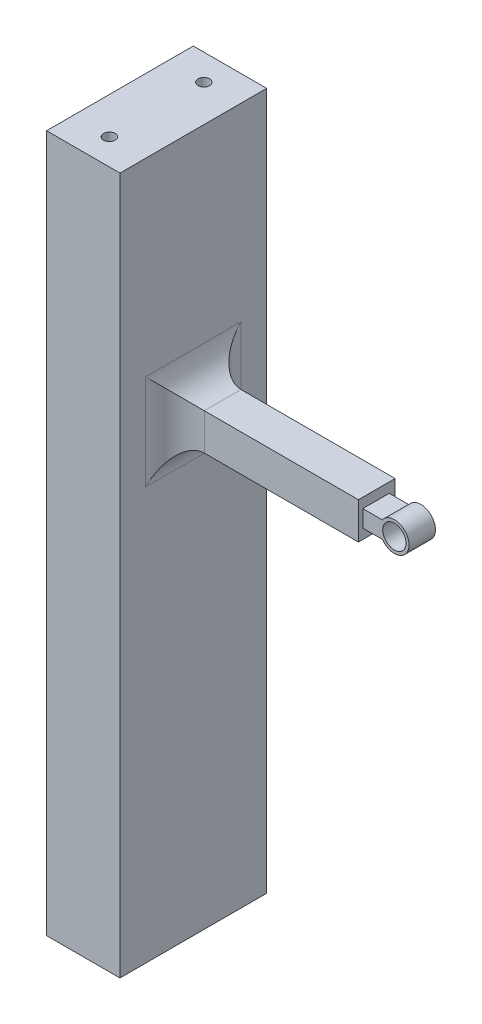
SolidWorks part; units mm, degrees
ref_plane "Front Plane" through (0, 0, 0) normal (0, 0, 1) x (1, 0, 0)
ref_plane "Top Plane" through (0, 0, 0) normal (0, 1, 0) x (1, 0, 0)
ref_plane "Right Plane" through (0, 0, 0) normal (1, 0, 0) x (0, 0, -1)
sketch "Sketch1" plane through (0, 0, 0) normal (0, 0, 1) x (1, 0, 0)
  line L0 (-112.8647, 1033.9699) -> (-112.8647, -66.0301)
  line L1 (-112.8647, 1033.9699) -> (-212.8647, 1033.9699)
  line L2 (-212.8647, 1033.9699) -> (-212.8647, -66.0301)
  line L3 (-212.8647, -66.0301) -> (-112.8647, -66.0301)
extrude "Boss-Extrude1" add sketch "Sketch1" along normal blind 200
sketch "Sketch2" plane through (-112.8647, 0, 0) normal (1, 0, 0) x (0, 0, -1)
  line L0 (-100, -66.0301) -> (-100, 710.9699)
  line L1 (-200, -66.0301) -> (0, -66.0301) construction
  dimension "D1" = 777
sketch "Sketch3" plane through (-112.8647, 0, 0) normal (1, 0, 0) x (0, 0, -1)
  line L1 (-125, 735.9699) -> (-75, 735.9699)
  line L2 (-125, 735.9699) -> (-125, 685.9699)
  line L3 (-125, 685.9699) -> (-75, 685.9699)
  line L4 (-75, 735.9699) -> (-75, 685.9699)
  line L5 (-125, 735.9699) -> (-75, 685.9699) construction
  line L6 (-125, 685.9699) -> (-75, 735.9699) construction
  point P0 (-100, 710.9699)
  dimension "D1" = 50
extrude "Boss-Extrude2" add sketch "Sketch3" along normal blind 250
fillet "Fillet1" radius 40 4 edges at (-112.8647, 735.9699, 100) (-112.8647, 685.9699, 100) (-112.8647, 710.9699, 75) (-112.8647, 710.9699, 125)
ref_plane "Plane1" through (0, 0, 125) normal (0, 0, 1) x (1, 0, 0)
sketch "Sketch4" plane through (0, 0, 125) normal (0, 0, 1) x (1, 0, 0)
  line L0 (137.1353, 710.9699) -> (137.1353, 722.4928)
  line L1 (137.1353, 722.4928) -> (163.7883, 722.4928)
  line L3 (137.1353, 735.9699) -> (137.1353, 685.9699) construction
  line L4 (137.1353, 710.9699) -> (137.1353, 699.447)
  line L5 (137.1353, 699.447) -> (163.7883, 699.447)
  circle A0 centre (180.1353, 710.9699) radius 20
  circle A1 centre (180.1353, 710.9699) radius 15.875
  arc A2 (163.7883, 722.4928) -> (163.7883, 699.447) centre (180.1353, 710.9699) ccw
  dimension "D1" = 43
extrude "Boss-Extrude3" add sketch "Sketch4" against normal blind 36 from offset 6 contours A0 L1 L0 L4 L5 | A0 A1 region at (149.2438, 710.9699, 125) region at (186.0084, 729.4955, 125) offset against normal yes
sketch "Sketch5" plane through (0, -66.0301, 0) normal (0, -1, 0) x (1, 0, 0)
  line L0 (-112.8647, 100) -> (-212.8647, 100)
  line L1 (-112.8647, 200) -> (-112.8647, 0) construction
  line L2 (-212.8647, 200) -> (-212.8647, 0) construction
  line L3 (-162.8647, 200) -> (-162.8647, 0) construction
  line L4 (-212.8647, 200) -> (-112.8647, 200) construction
  line L5 (-212.8647, 0) -> (-112.8647, 0) construction
  circle A0 centre (-162.8647, 100) radius 26
extrude "Cut-Extrude1" cut sketch "Sketch5" against normal blind 20 contours L3 L0 A0 | A0 L3 L0 | L0 L3 A0 | L3 A0 L0 region at (-151.83, -66.0301, 88.9653) region at (-151.83, -66.0301, 111.0347) region at (-173.8994, -66.0301, 88.9653) region at (-173.8994, -66.0301, 111.0347)
sketch "Sketch6" plane through (0, -66.0301, 0) normal (0, -1, 0) x (1, 0, 0)
  line L0 (-212.8647, 200) -> (-112.8647, 200)
  line L1 (-112.8647, 200) -> (-112.8647, 0)
  line L2 (-112.8647, 200) -> (-112.8647, 0) construction
  line L3 (-112.8647, 0) -> (-212.8647, 0)
  line L4 (-212.8647, 0) -> (-212.8647, 200)
extrude "Cut-Extrude2" cut sketch "Sketch6" against normal blind 150
sketch "Sketch7" plane through (0, 83.9699, 0) normal (0, -1, 0) x (1, 0, 0)
  line L0 (-112.8647, 100) -> (-212.8647, 100) construction
  line L1 (-112.8647, 35) -> (-112.8647, 165) construction
  line L2 (-212.8647, 200) -> (-212.8647, 0) construction
  line L3 (-162.8647, 200) -> (-162.8647, 0) construction
  line L4 (-112.8647, 200) -> (-212.8647, 200) construction
  line L5 (-212.8647, 0) -> (-112.8647, 0) construction
  circle A0 centre (-162.8647, 100) radius 26
extrude "Cut-Extrude3" cut sketch "Sketch7" against normal blind 40 contours A0
sketch "Sketch9" plane through (0, 1033.9699, 0) normal (0, 1, 0) x (1, 0, 0)
  line L0 (-162.8647, 0) -> (-162.8647, -200) construction
  line L1 (-112.8647, 0) -> (-212.8647, 0) construction
  line L2 (-112.8647, -200) -> (-212.8647, -200) construction
  line L3 (-112.8647, -100) -> (-212.8647, -100) construction
  line L4 (-112.8647, -200) -> (-112.8647, 0) construction
  line L5 (-212.8647, -200) -> (-212.8647, 0) construction
  line L6 (-162.8647, -100) -> (-162.8647, -164.3765)
  line L7 (-162.8647, -100) -> (-162.8647, -35.6235)
  circle A0 centre (-162.8647, -164.3765) radius 8
  circle A1 centre (-162.8647, -35.6235) radius 8
  dimension "D2" = 64.3765
  dimension "D1" = 64.3765
extrude "Cut-Extrude5" cut sketch "Sketch9" against normal blind 40 contours A0 region at (-157.3679, 1033.9699, 158.8796)
cosmetic thread "Cosmetic Thread3" parameters "D2"=18
extrude "Cut-Extrude6" cut sketch "Sketch9<4>" against normal blind 40 contours A1 region at (-168.3616, 1033.9699, 30.1266)
sketch "Sketch9<4>" plane through (0, 1033.9699, 0) normal (0, 1, 0) x (1, 0, 0) same geometry as "Sketch9"
cosmetic thread "Cosmetic Thread2" parameters "D2"=18
